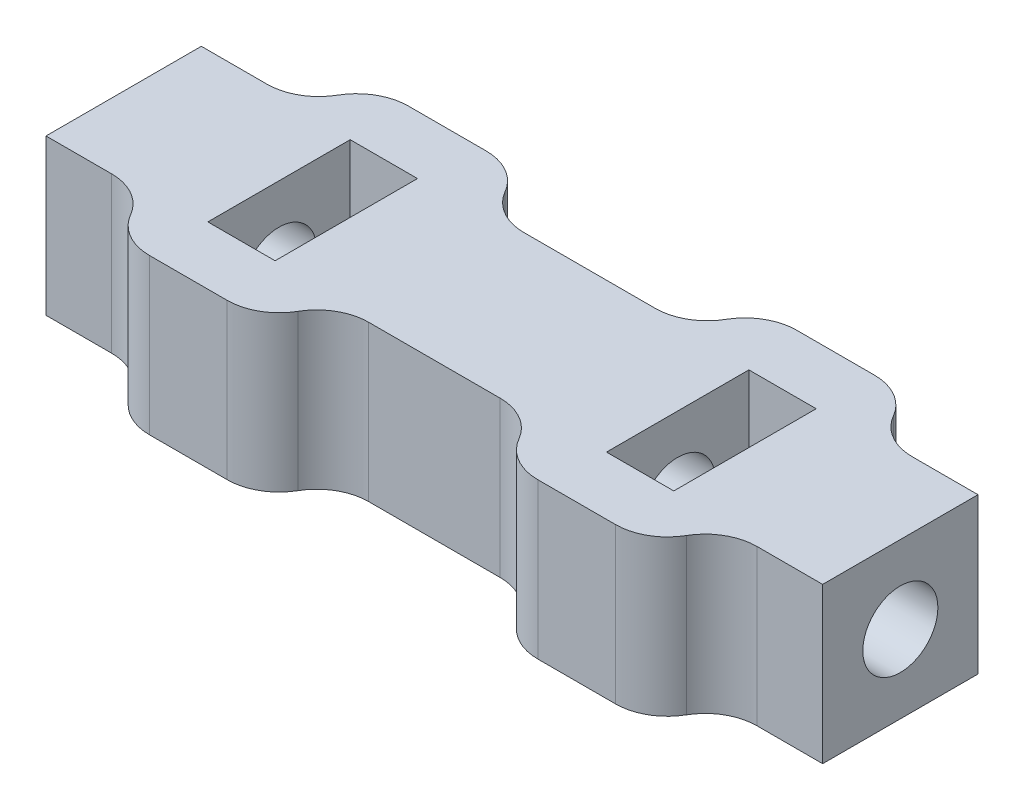
SolidWorks part; units mm, degrees
ref_plane "Front" through (0, 0, 0) normal (0, 0, 1) x (1, 0, 0)
ref_plane "Top" through (0, 0, 0) normal (0, 1, 0) x (1, 0, 0)
ref_plane "Right" through (0, 0, 0) normal (1, 0, 0) x (0, 0, -1)
sketch "Sketch1" plane through (0, 0, 0) normal (0, 0, 1) x (1, 0, 0)
  line L1 (0, 0) -> (30, 0)
  line L2 (0, 0) -> (0, -6)
  line L3 (0, -6) -> (30, -6)
  line L4 (30, 0) -> (30, -6)
  dimension "D1" = 6
  dimension "D2" = 30
extrude "Boss-Extrude1" add sketch "Sketch1" along normal blind 6
sketch "Sketch2" plane through (30, 0, 0) normal (1, 0, 0) x (0, 0, -1)
  line L0 (-6, -6) -> (-6, 0) construction
  line L1 (-6, 0) -> (0, 0) construction
  circle A0 centre (-3, -3) radius 1.45
  dimension "D1" = 2.9
  dimension "D2" = 3
  dimension "D3" = 3
extrude "Cut-Extrude1" cut sketch "Sketch2" against normal through all
sketch "Sketch3" plane through (0, 0, 0) normal (0, 1, 0) x (1, 0, 0)
  line L0 (0, -6) -> (0, 0) construction
  line L1 (6, -0.25) -> (8.6, -0.25)
  line L2 (6, -0.25) -> (6, -5.75)
  line L3 (6, -5.75) -> (8.6, -5.75)
  line L4 (8.6, -0.25) -> (8.6, -5.75)
  line L5 (21.4, -0.25) -> (24, -0.25)
  line L6 (21.4, -0.25) -> (21.4, -5.75)
  line L7 (21.4, -5.75) -> (24, -5.75)
  line L8 (24, -0.25) -> (24, -5.75)
  line L9 (30, -6) -> (30, 0) construction
  line L10 (30, 0) -> (0, 0) construction
  dimension "D1" = 2.6
  dimension "D2" = 5.5
  dimension "D3" = 2.6
  dimension "D4" = 5.5
  dimension "D5" = 6
  dimension "D6" = 6
  dimension "D7" = 0.25
  dimension "D8" = 0.25
extrude "Cut-Extrude2" cut sketch "Sketch3" against normal through all
sketch "Sketch4" plane through (0, 0, 0) normal (0, 1, 0) x (1, 0, 0)
  line L0 (30, -6) -> (0, -6) construction
  line L1 (4, -6) -> (11, -6)
  line L2 (4, -6) -> (4, -8)
  line L3 (4, -8) -> (11, -8)
  line L4 (11, -6) -> (11, -8)
  line L5 (30, 0) -> (0, 0) construction
  line L6 (19, -6) -> (26, -6)
  line L7 (19, -6) -> (19, -8)
  line L8 (19, -8) -> (26, -8)
  line L9 (26, -6) -> (26, -8)
  line L10 (4, 0) -> (11, 0)
  line L11 (4, 0) -> (4, 2)
  line L12 (4, 2) -> (11, 2)
  line L13 (11, 0) -> (11, 2)
  line L14 (30, -6) -> (30, 0) construction
  line L15 (19, 0) -> (26, 0)
  line L16 (19, 0) -> (19, 2)
  line L17 (19, 2) -> (26, 2)
  line L18 (26, 0) -> (26, 2)
  line L19 (0, -6) -> (0, 0) construction
  dimension "D1" = 2
  dimension "D2" = 2
  dimension "D3" = 2
  dimension "D4" = 2
  dimension "D5" = 7
  dimension "D6" = 7
  dimension "D7" = 7
  dimension "D8" = 7
  dimension "D9" = 4
  dimension "D10" = 4
  dimension "D11" = 4
  dimension "D12" = 4
extrude "Boss-Extrude2" add sketch "Sketch4" against normal blind 6
fillet "Fillet1" radius 2 8 edges at (26, -3, -2) (4, -3, -2) (11, -3, -2) (19, -3, -2) (26, -3, 8) (19, -3, 8) (11, -3, 8) (4, -3, 8)
fillet "Fillet2" radius 2 8 edges at (19, -3, 6) (26, -3, 6) (11, -3, 6) (4, -3, 6) (4, -3, 0) (26, -3, 0) (19, -3, 0) (11, -3, 0)
equation "\"D7@Sketch3\"=(\"D1@Boss-Extrude1\"-\"D4@Sketch3\")/2"
equation "\"D8@Sketch3\"=\"D7@Sketch3\""
